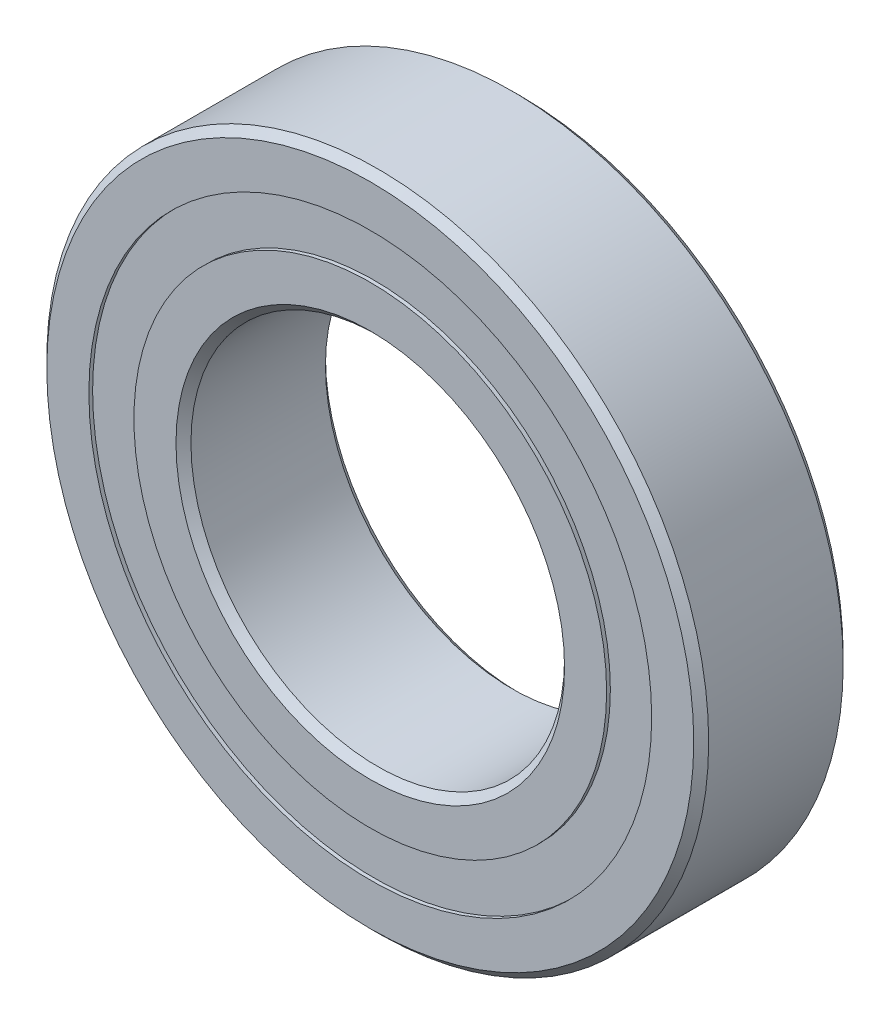
SolidWorks part; units mm, degrees
ref_plane "Front Plane" through (0, 0, 0) normal (0, 0, 1) x (1, 0, 0)
ref_plane "Top Plane" through (0, 0, 0) normal (0, 1, 0) x (1, 0, 0)
ref_plane "Right Plane" through (0, 0, 0) normal (1, 0, 0) x (0, 0, -1)
sketch "Sketch1" plane through (0, 0, 0) normal (1, 0, 0) x (0, 0, -1)
  line L0 (-7, 0) -> (7, 0) construction
  line L1 (0, 31) -> (0, -31) construction
  line L2 (6.3, 31) -> (-6.3, 31)
  line L3 (-6.3, 31) -> (-7, 30.3)
  line L4 (-7, 30.3) -> (-7, 26.3596)
  line L5 (-7, 26.3596) -> (-3.1111, 26.3596)
  line L6 (7, 26.3596) -> (3.1111, 26.3596)
  line L7 (7, 30.3) -> (7, 26.3596)
  line L8 (6.3, 31) -> (7, 30.3)
  line L9 (0, 31) -> (0, 24.2497) construction
  line L10 (0, 24.2497) -> (0, 17.4995) construction
  arc A0 (-3.1111, 26.3596) -> (3.1111, 26.3596) centre (0, 24.2497) cw
  point P14 (0, 17.4995)
  dimension "Width" = 14
  dimension "OD" = 62
  dimension "D1" = 45
  dimension "D2" = 0.7
  dimension "Shaft Dia" = 34.999
  dimension "D3" = 6.2222
  dimension "D4" = 2.1099
revolve "Revolve1" add sketch "Sketch1" angle 360 about L0
sketch "Sketch3" plane through (0, 0, 0) normal (1, 0, 0) x (0, 0, -1)
  line L0 (-7, 22.1399) -> (-3.1111, 22.1399)
  line L1 (0, 31) -> (0, -31) construction
  line L2 (-7, 30.3) -> (-7, 26.3596) construction
  line L3 (-7, 22.1399) -> (-7, 18.1995)
  line L4 (-6.3, 31) -> (-7, 30.3) construction
  line L5 (-7, 18.1995) -> (-6.3, 17.4995)
  line L6 (-6.3, 17.4995) -> (6.3, 17.4995)
  line L7 (6.3, 31) -> (6.3, -31) construction
  line L8 (6.3, 17.4995) -> (7, 18.1995)
  line L9 (7, -30.3) -> (7, 30.3) construction
  line L10 (7, 18.1995) -> (7, 22.1399)
  line L11 (7, 22.1399) -> (3.1111, 22.1399)
  line L13 (6.3, 31) -> (7, 30.3) construction
  arc A0 (3.1111, 26.3596) -> (-3.1111, 26.3596) centre (0, 24.2497) ccw construction
  arc A1 (3.1111, 22.1399) -> (-3.1111, 22.1399) centre (0, 24.2497) cw
revolve "Revolve3" add sketch "Sketch3" angle 360 about L0
sketch "Sketch4" plane through (0, 0, 0) normal (1, 0, 0) x (0, 0, -1)
  line L0 (-3.7591, 24.2497) -> (3.7591, 24.2497)
  arc A2 (-3.7591, 24.2497) -> (3.7591, 24.2497) centre (0, 24.2497) cw
  arc A3 (3.1111, 26.3596) -> (-3.1111, 26.3596) centre (0, 24.2497) ccw construction
revolve "Revolve4" add sketch "Sketch4" angle 360 about L0
ref_axis "Axis1" through (0, 0, -7) along (0, 0, 1)
pattern_circular "CirPattern1" count 12 every 30 about axis through (0, 0, -7) along (0, 0, 1) of bodies 104
sketch "Sketch5" plane through (0, 0, 0) normal (1, 0, 0) x (0, 0, -1)
  line L0 (-7, 26.3596) -> (-3.1111, 26.3596) construction
  line L1 (-6.65, 26.3596) -> (-3.7591, 26.3596)
  line L2 (-6.65, 26.3596) -> (-6.65, 22.1399)
  line L3 (-6.65, 22.1399) -> (-3.7591, 22.1399)
  line L4 (-3.7591, 26.3596) -> (-3.7591, 22.1399)
  line L5 (-7, 22.1399) -> (-3.1111, 22.1399) construction
  line L6 (7, 26.3596) -> (3.1111, 26.3596) construction
  line L7 (6.65, 26.3596) -> (3.7591, 26.3596)
  line L8 (6.65, 26.3596) -> (6.65, 22.1399)
  line L9 (6.65, 22.1399) -> (3.7591, 22.1399)
  line L10 (3.7591, 26.3596) -> (3.7591, 22.1399)
  line L11 (7, 22.1399) -> (3.1111, 22.1399) construction
  line L12 (-6.3, 31) -> (-7, 30.3) construction
  point P18 (-6.65, 30.65)
revolve "Revolve5" add sketch "Sketch5" angle 360 about L0
equation "\"D2@Sketch1\" = \"Width@Sketch1\"*.05"
equation "\"D3@Sketch1\" = \"Width@Sketch1\"/2.25"
equation "\"D4@Sketch1\" = (((\"OD@Sketch1\"-\"Width@Sketch1\")/2)/3.25)/3.5"
equation "\"D2@CirPattern1\" = 360/\"Balls@CirPattern1\""
